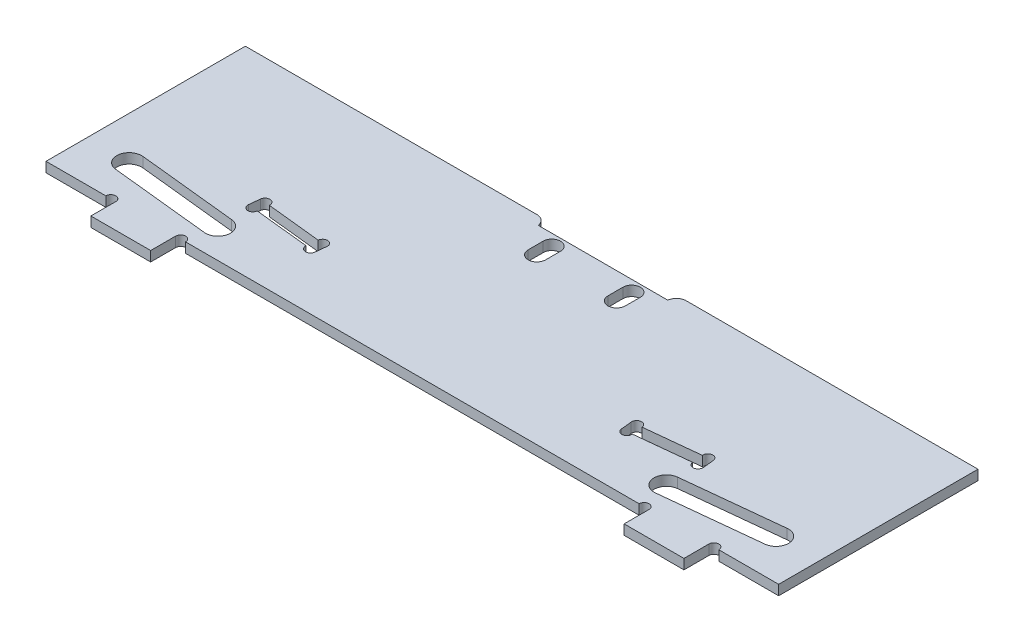
SolidWorks part; units mm, degrees
ref_plane "前视基准面" through (0, 0, 0) normal (0, 0, 1) x (1, 0, 0)
ref_plane "上视基准面" through (0, 0, 0) normal (0, 1, 0) x (1, 0, 0)
ref_plane "右视基准面" through (0, 0, 0) normal (1, 0, 0) x (0, 0, -1)
sketch "草图1" plane through (0, 0, 0) normal (0, 1, 0) x (1, 0, 0)
  line L1 (-73.5, 20) -> (73.5, 20)
  line L2 (-73.5, 20) -> (-73.5, -20)
  line L3 (-73.5, -20) -> (73.5, -20)
  line L4 (73.5, 20) -> (73.5, -20)
  line L5 (-73.5, 20) -> (73.5, -20) construction
  line L6 (-73.5, -20) -> (73.5, 20) construction
  point P0 (0, 0)
  dimension "D1" = 147
  dimension "D2" = 40
extrude "凸台-拉伸1" add sketch "草图1" along normal blind 2
sketch "草图2" plane through (0, 2, 0) normal (0, 1, 0) x (1, 0, 0)
  line L0 (-45.6587, -7.223) -> (-45.4288, -5.0351)
  line L1 (-45.4288, -5.0351) -> (-30.5109, -6.603)
  line L2 (-30.5109, -6.603) -> (-30.7409, -8.791)
  line L3 (-30.7409, -8.791) -> (-45.6587, -7.223)
  line L4 (-73.5, -20) -> (73.5, -20) construction
  dimension "D1" = 8.791
  dimension "D2" = 30.7409
  dimension "D3" = 15
  dimension "D4" = 2.2
  dimension "D5" = 6
extrude "切除-拉伸1" cut sketch "草图2" against normal through all
sketch "草图3" plane through (0, 2, 0) normal (0, 1, 0) x (1, 0, 0)
  line L0 (-30.5109, -6.603) -> (-45.4288, -5.0351) construction
  line L1 (-45.6587, -7.223) -> (-30.7409, -8.791) construction
  line L2 (-45.4288, -5.0351) -> (-45.6587, -7.223) construction
  line L3 (-30.7409, -8.791) -> (-30.5109, -6.603) construction
  circle A0 centre (-44.4342, -5.1396) radius 1
  circle A1 centre (-44.6642, -7.3276) radius 1
  circle A2 centre (-31.5055, -6.4985) radius 1
  circle A3 centre (-31.7354, -8.6864) radius 1
  dimension "D1" = 2
extrude "切除-拉伸2" cut sketch "草图3" against normal through all
mirror "镜向1" about plane through (0, 0, 0) normal (1, 0, 0) of "切除-拉伸1", "切除-拉伸2"
sketch "草图5" plane through (0, 0, 20) normal (0, 0, 1) x (1, 0, 0)
  line L0 (-73.5, 0) -> (73.5, 0) construction
  line L1 (59.5, 0) -> (47.5, 0)
  line L2 (59.5, 0) -> (59.5, 2)
  line L3 (59.5, 2) -> (47.5, 2)
  line L4 (47.5, 0) -> (47.5, 2)
  line L5 (-73.5, 2) -> (73.5, 2) construction
  line L6 (-73.5, 2) -> (-73.5, 0) construction
  line L7 (-59.5, 2) -> (-47.5, 2)
  line L8 (-59.5, 2) -> (-59.5, 0)
  line L9 (-59.5, 0) -> (-47.5, 0)
  line L10 (-47.5, 2) -> (-47.5, 0)
  line L11 (73.5, 2) -> (73.5, 0) construction
  dimension "D1" = 14
  dimension "D2" = 14
  dimension "D3" = 12
  dimension "D4" = 12
extrude "凸台-拉伸2" add sketch "草图5" along normal blind 5
sketch "草图7" plane through (0, 2, 0) normal (0, 1, 0) x (1, 0, 0)
  line L0 (59.5, -20) -> (73.5, -20) construction
  line L1 (-47.5, -20) -> (47.5, -20) construction
  line L2 (-73.5, -20) -> (-59.5, -20) construction
  line L3 (-59.5, -25) -> (-59.5, -20) construction
  line L4 (-47.5, -25) -> (-47.5, -20) construction
  line L5 (47.5, -25) -> (47.5, -20) construction
  line L6 (59.5, -25) -> (59.5, -20) construction
  circle A0 centre (60.5, -20) radius 1
  circle A1 centre (46.5, -20) radius 1
  circle A2 centre (-46.5, -20) radius 1
  circle A3 centre (-60.5, -20) radius 1
  dimension "D1" = 2
extrude "切除-拉伸3" cut sketch "草图7" against normal through all
sketch "草图10" plane through (0, 2, 0) normal (0, 1, 0) x (1, 0, 0)
  line L0 (-64.8904, -11.9094) -> (-45, -14) construction
  line L1 (-64.6291, -9.4231) -> (-44.7387, -11.5137)
  line L2 (-65.1518, -14.3957) -> (-45.2613, -16.4863)
  line L3 (-43.6697, -7.4321) -> (-32.7299, -8.5819) construction
  arc A0 (-64.6291, -9.4231) -> (-65.1518, -14.3957) centre (-64.8904, -11.9094) ccw
  arc A1 (-45.2613, -16.4863) -> (-44.7387, -11.5137) centre (-45, -14) ccw
  point P2 (-54.9452, -12.9547)
  dimension "D2" = 2.5
  dimension "D1" = 20
  dimension "D3" = 45
  dimension "D4" = 14
extrude "切除-拉伸5" cut sketch "草图10" against normal through all
mirror "镜向2" about plane through (0, 0, 0) normal (1, 0, 0) of "切除-拉伸5"
sketch "草图11" plane through (0, 2, 0) normal (0, 1, 0) x (1, 0, 0)
  line L0 (73.5, 20) -> (-73.5, 20) construction
  line L1 (-13, 21.75) -> (13, 21.75)
  line L2 (-13, 21.75) -> (-13, 18.25)
  line L3 (-13, 18.25) -> (13, 18.25)
  line L4 (13, 21.75) -> (13, 18.25)
  line L5 (-13, 21.75) -> (13, 18.25) construction
  line L6 (-13, 18.25) -> (13, 21.75) construction
  point P0 (0, 20)
  dimension "D1" = 3.5
  dimension "D2" = 26
extrude "切除-拉伸6" cut sketch "草图11" against normal blind 10
fillet "圆角1" radius 2 2 edges at (13, 1, -20) (-13, 1, -20)
sketch "草图12" plane through (0, 2, 0) normal (0, 1, 0) x (1, 0, 0)
  line L0 (-8, 16) -> (-8, 13) construction
  line L1 (-6.25, 16) -> (-6.25, 13)
  line L2 (-9.75, 16) -> (-9.75, 13)
  line L3 (8, 16) -> (8, 13) construction
  line L4 (9.75, 16) -> (9.75, 13)
  line L5 (6.25, 16) -> (6.25, 13)
  line L6 (8, 16) -> (-8, 16) construction
  arc A0 (-6.25, 16) -> (-9.75, 16) centre (-8, 16) ccw
  arc A1 (-9.75, 13) -> (-6.25, 13) centre (-8, 13) ccw
  arc A2 (9.75, 16) -> (6.25, 16) centre (8, 16) ccw
  arc A3 (6.25, 13) -> (9.75, 13) centre (8, 13) ccw
  point P2 (-8, 14.5)
  point P7 (8, 14.5)
  dimension "D1" = 1.75
  dimension "D2" = 16
  dimension "D3" = 16
  dimension "D4" = 8
  dimension "D5" = 3
extrude "切除-拉伸7" cut sketch "草图12" against normal through all
